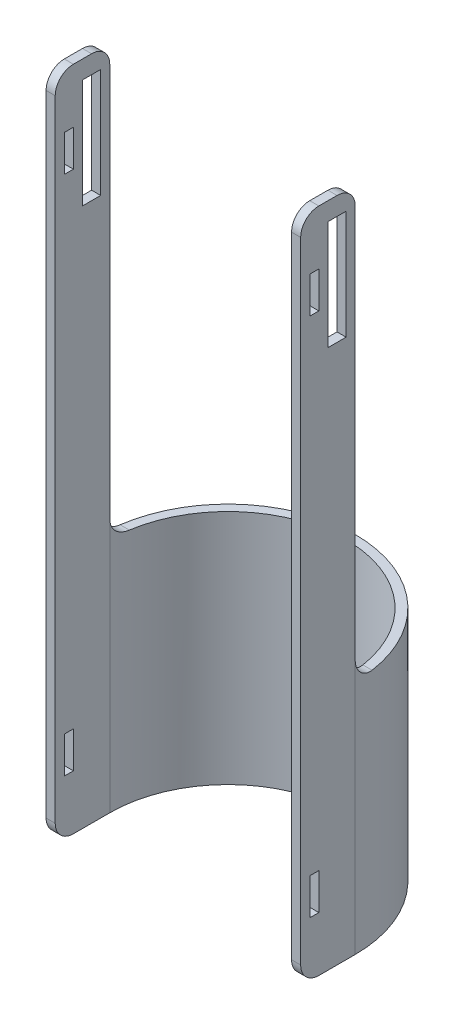
SolidWorks part; units mm, degrees
material "PE High Density"
ref_plane "Front Plane" through (0, 0, 0) normal (0, 0, 1) x (1, 0, 0)
ref_plane "Top Plane" through (0, 0, 0) normal (0, 1, 0) x (1, 0, 0)
ref_plane "Right Plane" through (0, 0, 0) normal (1, 0, 0) x (0, 0, -1)
sketch "Sketch1" plane through (0, 0, 0) normal (0, 1, 0) x (1, 0, 0)
  line L0 (-70, 0) -> (70, 0) construction
  line L1 (-65, 0) -> (-70, 0)
  line L2 (70, 0) -> (65, 0)
  arc A0 (70, 0) -> (-70, 0) centre (0, 0) ccw
  arc A1 (65, 0) -> (-65, 0) centre (0, 0) ccw
  dimension "D1" = 65
  dimension "D2" = 70
extrude "Boss-Extrude1" add sketch "Sketch1" along normal blind 130.0689
sketch "Sketch2" plane through (0, 0, 0) normal (0, 0, 1) x (1, 0, 0)
  line L1 (65, 130.0689) -> (70, 130.0689)
  line L2 (65, 130.0689) -> (65, 0)
  line L3 (65, 0) -> (70, 0)
  line L4 (70, 130.0689) -> (70, 0)
  line L5 (-70, 130.0689) -> (-65, 130.0689)
  line L6 (-70, 130.0689) -> (-70, 0)
  line L7 (-70, 0) -> (-65, 0)
  line L8 (-65, 130.0689) -> (-65, 0)
extrude "Boss-Extrude2" add sketch "Sketch2" along normal blind 30
sketch "Sketch3" plane through (0, 130.0689, 0) normal (0, 1, 0) x (1, 0, 0)
  line L1 (-65, -30) -> (-70, -30)
  line L2 (-65, -30) -> (-65, 0)
  line L3 (-65, 0) -> (-70, 0)
  line L4 (-70, -30) -> (-70, 0)
  line L5 (70, -30) -> (65, -30)
  line L6 (70, -30) -> (70, 0)
  line L7 (70, 0) -> (65, 0)
  line L8 (65, -30) -> (65, 0)
extrude "Boss-Extrude3" add sketch "Sketch3" along normal blind 236.5
sketch "Sketch5" plane through (-70, 0, 0) normal (-1, 0, 0) x (0, 0, 1)
  line L0 (0, 366.5689) -> (30, 366.5689) construction
  line L1 (5, 356.5689) -> (15, 356.5689)
  line L2 (5, 356.5689) -> (5, 296.5689)
  line L3 (5, 296.5689) -> (15, 296.5689)
  line L4 (15, 356.5689) -> (15, 296.5689)
  line L5 (0, 366.5689) -> (0, 130.0689) construction
  dimension "D1" = 60
  dimension "D2" = 10
  dimension "D3" = 10
  dimension "D4" = 5
extrude "Cut-Extrude1" cut sketch "Sketch5" against normal blind 240
sketch "Sketch6" plane through (-70, 0, 0) normal (-1, 0, 0) x (0, 0, 1)
  line L0 (17.5605, 360) -> (17.5605, 300) construction
  line L1 (20, 336.5689) -> (25, 336.5689)
  line L2 (20, 336.5689) -> (20, 316.5689)
  line L3 (20, 316.5689) -> (25, 316.5689)
  line L4 (25, 336.5689) -> (25, 316.5689)
  line L5 (15, 356.5689) -> (5, 356.5689) construction
  line L7 (15, 296.5689) -> (15, 356.5689) construction
  dimension "D1" = 20
  dimension "D2" = 5
  dimension "D3" = 20
  dimension "D4" = 5
extrude "Cut-Extrude2" cut sketch "Sketch6" against normal through all
fillet "Fillet1" radius 10 4 edges at (67.5, 366.5689, 30) (-67.5, 366.5689, 30) (-67.5, 366.5689, 0) (67.5, 366.5689, 0)
fillet "Fillet2" radius 10 2 edges at (67.5, 0, 30) (-67.5, 0, 30)
fillet "Fillet3" radius 10 2 edges at (67.5, 130.0689, 0) (-67.5, 130.0689, 0)
sketch "Sketch8" plane through (-70, 0, 0) normal (-1, 0, 0) x (0, 0, 1)
  line L1 (20, 50) -> (25, 50)
  line L2 (20, 50) -> (20, 30)
  line L3 (20, 30) -> (25, 30)
  line L4 (25, 50) -> (25, 30)
  line L5 (20, 0) -> (0, 0) construction
  line L6 (30, 356.5689) -> (30, 10) construction
  dimension "D1" = 20
  dimension "D2" = 5
  dimension "D3" = 30
  dimension "D4" = 5
extrude "Cut-Extrude3" cut sketch "Sketch8" against normal through all
ref_plane "Plane1" through (0, 65.0689, 0) normal (0, 1, 0) x (1, 0, 0)
sketch "Sketch9" plane through (0, 65.0689, 0) normal (0, 1, 0) x (1, 0, 0)
  line L0 (-21.6312, 66.574) -> (-21.6312, 76.574)
  line L1 (-21.6312, 76.574) -> (21.6312, 76.574)
  line L2 (21.6312, 76.574) -> (21.6312, 66.574)
  line L3 (-70, 0) -> (70, 0)
  line L4 (0, 0) -> (-21.6312, 66.574) construction
  line L5 (0, 0) -> (21.6312, 66.574) construction
  arc A0 (69.282, 10) -> (-69.282, 10) centre (0, 0) ccw construction
  arc A1 (70, 0) -> (-21.6312, 66.574) centre (0, 0) ccw
  point P13 (0, 0)
  dimension "D1" = 72
  dimension "D2" = 72
  dimension "D3" = 10
  dimension "D4" = 10
extrude "Boss-Extrude4" add sketch "Sketch9" along normal mid plane 60 contours A1 L2 L1 L0 region at (0, 65.0689, -72.6545)
fillet "Fillet4" radius 5 4 edges at (0, 35.0689, -76.574) (21.6312, 65.0689, -76.574) (-21.6312, 65.0689, -76.574) (0, 95.0689, -76.574)
sketch "Sketch10" plane through (0, 0, -76.574) normal (0, 0, -1) x (-1, 0, 0)
  line L0 (16.6312, 90.0689) -> (-16.6312, 90.0689) construction
  line L1 (-16.6312, 90.0689) -> (-16.6312, 40.0689) construction
  line L2 (16.6312, 40.0689) -> (16.6312, 90.0689) construction
  line L3 (16.6312, 90.0689) -> (-16.6312, 90.0689) construction
  line L4 (-16.6312, 40.0689) -> (16.6312, 40.0689) construction
  line L5 (-16.6312, 40.0689) -> (16.6312, 40.0689) construction
  circle A0 centre (-11.6312, 85.0689) radius 1.0922
  circle A1 centre (11.6312, 85.0689) radius 1.0922
  circle A2 centre (-11.6312, 45.0689) radius 1.0922
  circle A3 centre (11.6312, 45.0689) radius 1.0922
  dimension "D1" = 2.1844
  dimension "D2" = 2.1844
  dimension "D3" = 2.1844
  dimension "D4" = 2.1844
  dimension "D5" = 5
  dimension "D7" = 5
  dimension "D8" = 5
  dimension "D9" = 5
  dimension "D10" = 5
  dimension "D11" = 5
  dimension "D12" = 5
  dimension "D6" = 5
extrude "Cut-Extrude4" cut sketch "Sketch10" against normal blind 5
cosmetic thread "Cosmetic Thread6" parameters "D2"=3.1844
cosmetic thread "Cosmetic Thread7" parameters "D2"=3.1844
cosmetic thread "Cosmetic Thread8" parameters "D2"=3.1844
cosmetic thread "Cosmetic Thread9" parameters "D2"=3.1844
equation "\"userHeight\" = 1700mm'Users height"
equation "\"shellLength\"= \"userHeight\" / 13.07'Shell Length"
equation "\"D1@Boss-Extrude1\"=\"shellLength\""
equation "\"partialSidebarLength\"= \"userHeight\" * 0.245 - 180'Sidebar length - minus constant"
equation "\"shell_outer_radius\"= IIF ( \"userHeight\" > 1850 , 86 , 70 )'Shell outer radius"
equation "\"D2@Sketch1\"=\"shell_outer_radius\""
equation "\"shell_inner_radius\"= IIF ( \"userHeight\" > 1850 , 77 , 65 )'Shell inner radius"
equation "\"D1@Sketch1\"=\"shell_inner_radius\""
equation "\"fin_platform_extrusion\"= 60 * \"userHeight\" / 1700'Fin platform height"
equation "\"D1@Boss-Extrude4\"=\"fin_platform_extrusion\""
equation "\"D1@Boss-Extrude3\"=\"partialSidebarLength\""
